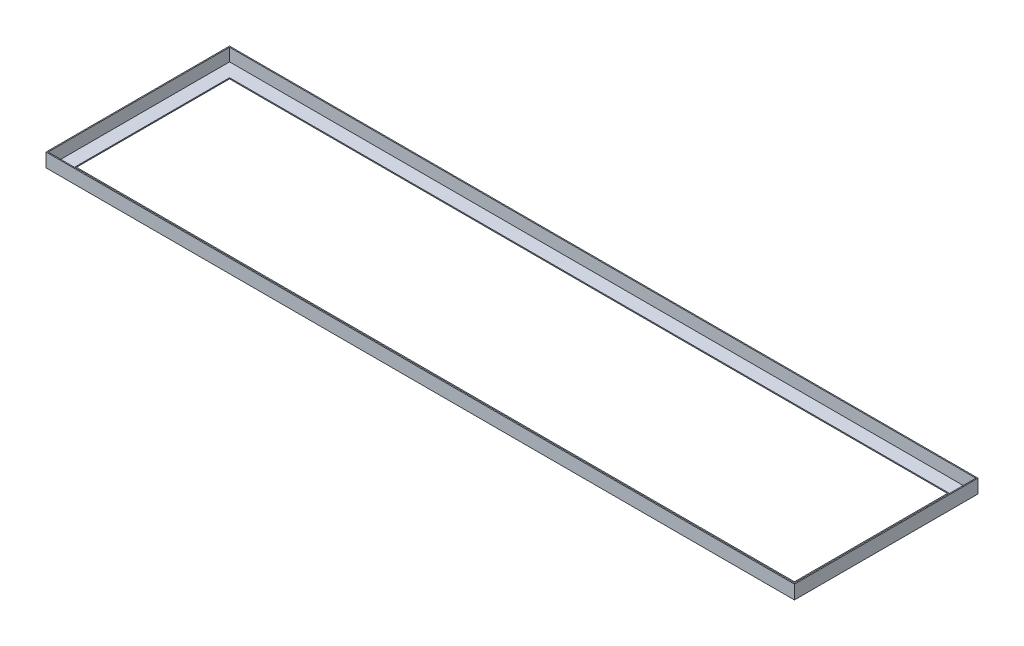
SolidWorks part; units mm, degrees
ref_plane "Front Plane" through (0, 0, 0) normal (0, 0, 1) x (1, 0, 0)
ref_plane "Top Plane" through (0, 0, 0) normal (0, 1, 0) x (1, 0, 0)
ref_plane "Right Plane" through (0, 0, 0) normal (1, 0, 0) x (0, 0, -1)
sketch "Sketch1" plane through (0, 0, 0) normal (0, 1, 0) x (1, 0, 0)
  line L0 (-1087, 264.32) -> (1087, 264.32)
  line L1 (-1090, 267.32) -> (1090, 267.32)
  line L2 (-1090, 267.32) -> (-1090, -267.32)
  line L3 (-1090, -267.32) -> (1090, -267.32)
  line L4 (1090, 267.32) -> (1090, -267.32)
  line L5 (-1090, 267.32) -> (1090, -267.32) construction
  line L6 (-1090, -267.32) -> (1090, 267.32) construction
  line L7 (1087, 264.32) -> (1087, -264.32)
  line L8 (-1087, -264.32) -> (1087, -264.32)
  line L9 (-1087, 264.32) -> (-1087, -264.32)
  line L10 (-1047, 224.32) -> (-1047, -224.32)
  line L11 (-1047, -224.32) -> (1047, -224.32)
  line L12 (1047, 224.32) -> (1047, -224.32)
  line L13 (-1047, 224.32) -> (1047, 224.32)
  point P0 (0, 0)
  dimension "D1" = 2180
  dimension "D2" = 534.64
  dimension "D3" = 3
  dimension "D4" = 40
extrude "Boss-Extrude1" add sketch "Sketch1" along normal blind 40 contours L4 L1 L2 L3 L9 L0 L7 L8 region at (0, 0, -265.0754)
extrude "Boss-Extrude2" add sketch "Sketch1<3>" along normal blind 3 contours L0 L9 L8 L7 L10 L13 L12 L11 region at (0, 0, -241.9465)
sketch "Sketch1<3>" plane through (0, 0, 0) normal (0, 1, 0) x (1, 0, 0) same geometry as "Sketch1"
